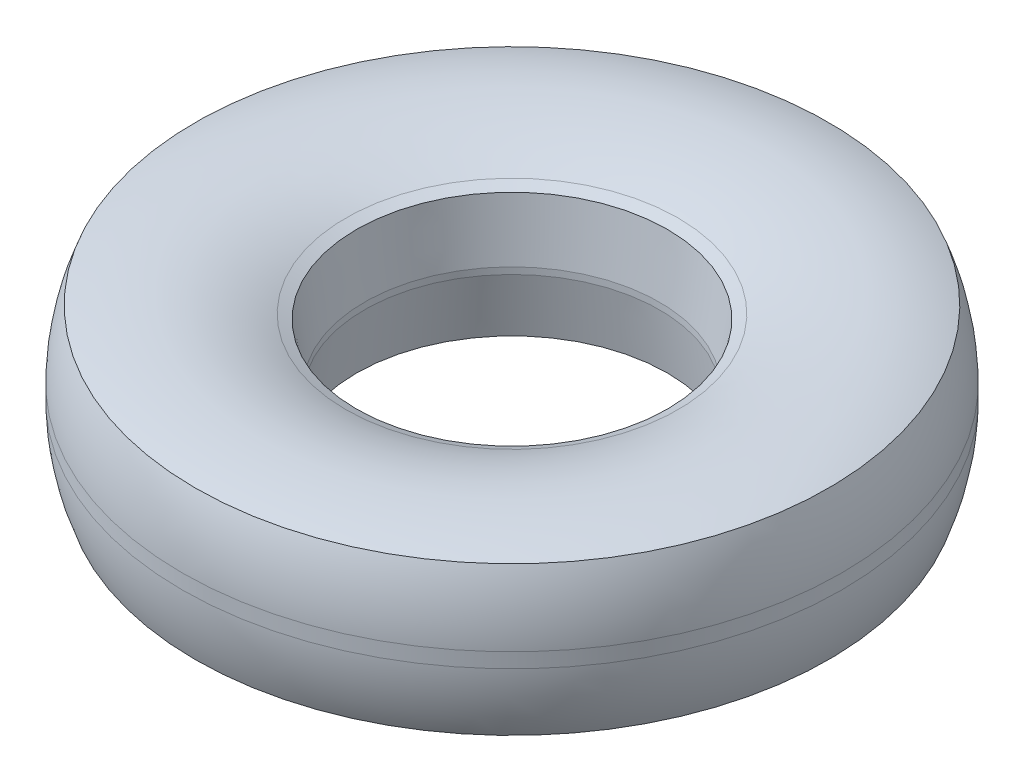
SolidWorks part; units mm, degrees
material "Rubber"
ref_plane "Front Plane" through (0, 0, 0) normal (0, 0, 1) x (1, 0, 0)
ref_plane "Top Plane" through (0, 0, 0) normal (0, 1, 0) x (1, 0, 0)
ref_plane "Right Plane" through (0, 0, 0) normal (1, 0, 0) x (0, 0, -1)
sketch "Sketch1" plane through (0, 0, 0) normal (0, 0, 1) x (1, 0, 0)
  line L0 (-69.85, 0) -> (-73.66, 27.94) construction
  line L1 (-73.66, 27.94) -> (-79.375, 30.48) construction
  line L2 (-153.5508, 0.6476) -> (-153.5508, -6.3626)
  line L3 (-70.9586, -1.27) -> (-74.8227, 27.067)
  line L4 (-69.85, 0) -> (-3.561, 0) construction
  line L5 (-74.8227, 27.067) -> (-79.8908, 29.3194)
  line L6 (-85.7418, -2.8575) -> (23.0582, -2.8575) construction
  line L7 (-79.4735, -29.2899) -> (-81.954, -30.3923)
  line L8 (-70.9586, -4.4451) -> (-74.8227, -32.782)
  line L9 (-74.8227, -32.782) -> (-79.8908, -35.0345)
  line L10 (-158.6308, 0.6873) -> (-158.6308, -6.4023)
  line L11 (-70.9586, -1.27) -> (-70.9586, -4.4451)
  line L12 (-76.0386, -4.1003) -> (-79.4735, -29.2899)
  line L13 (-70.9586, -1.27) -> (-3.561, -1.27) construction
  line L14 (-76.0386, -1.6148) -> (-76.0386, -4.1003)
  line L15 (-76.0386, -1.6148) -> (-79.4735, 23.5749)
  line L16 (-79.4735, 23.5749) -> (-81.954, 24.6773)
  line L17 (0, 35.0445) -> (0, -64.0726) construction
  arc A0 (-79.8908, 29.3194) -> (-152.3201, 32.8917) centre (-120.7251, -62.5582) ccw
  arc A1 (-152.3201, 32.8917) -> (-158.6308, 0.6873) centre (-66.0247, -0.7389) ccw
  arc A2 (-79.8908, -35.0345) -> (-152.3201, -38.6068) centre (-120.7251, 56.8431) cw
  arc A3 (-152.3201, -38.6068) -> (-158.6308, -6.4023) centre (-66.0247, -4.9762) cw
  arc A4 (-148.4284, 28.7969) -> (-153.5508, 0.6476) centre (-66.0247, -0.7389) ccw
  arc A5 (-148.4284, -34.5119) -> (-153.5508, -6.3626) centre (-66.0247, -4.9762) cw
  arc A6 (-81.954, -30.3923) -> (-148.4284, -34.5119) centre (-120.7251, 56.8431) cw
  arc A7 (-81.954, 24.6773) -> (-148.4284, 28.7969) centre (-120.7251, -62.5582) ccw
  point P14 (-162.3296, -5.6627)
  point P16 (-115.9588, 39.4335)
  point P17 (-152.3201, 32.8917)
  dimension "D1" = 69.85
  dimension "D2" = 27.94
  dimension "D3" = 73.66
  dimension "D4" = 79.375
  dimension "D5" = 64.3539
  dimension "D7" = 5.08
  dimension "D8" = 78.74
  dimension "D9" = 42.291
  dimension "D10" = 36.068
  dimension "D11" = 10.0095
  dimension "D12" = 6.35
  dimension "D13" = 59.849
  dimension "D6" = 1.27
revolve "Revolve2" add sketch "Sketch1" angle 360 about L17
ref_plane "Plane1" through (-158.6308, 0, 0) normal (-1, 0, 0) x (0, 0, 1)
sketch "Sketch4" plane through (0, 0, 0) normal (1, 0, 0) x (0, 0, -1)
  line L0 (-158.6308, 0.6873) -> (-158.6308, -6.4023)
  arc A0 (-152.3201, 32.8917) -> (-158.6308, 0.6873) centre (-66.0247, -0.7389) ccw
  arc A1 (-152.3201, -38.6068) -> (-158.6308, -6.4023) centre (-66.0247, -4.9762) cw
